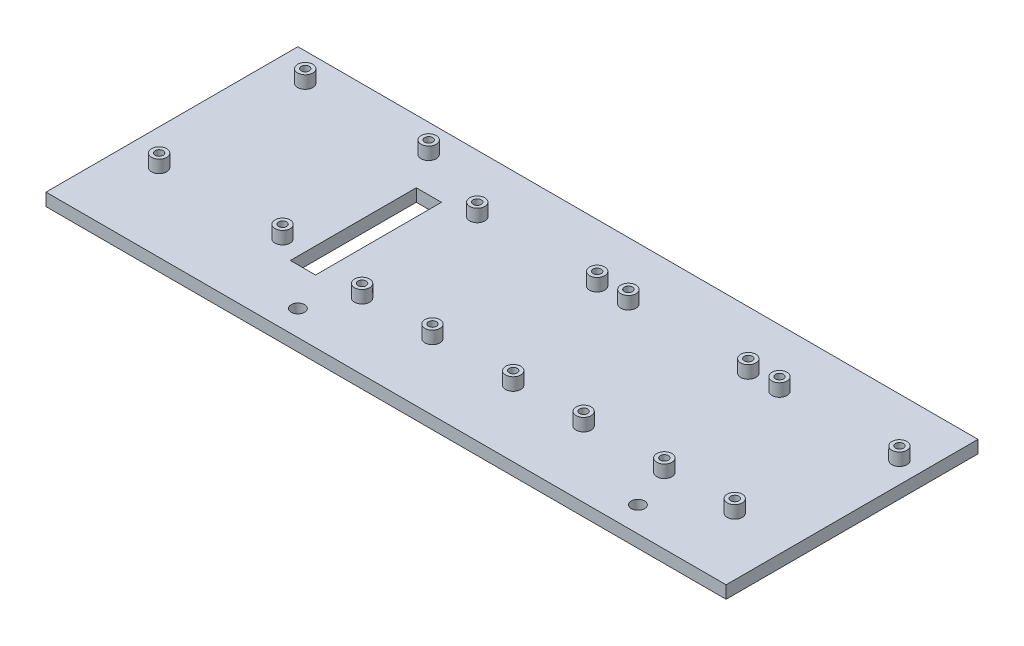
SolidWorks part; units mm, degrees
ref_plane "Front Plane" through (0, 0, 0) normal (0, 0, 1) x (1, 0, 0)
ref_plane "Top Plane" through (0, 0, 0) normal (0, 1, 0) x (1, 0, 0)
ref_plane "Right Plane" through (0, 0, 0) normal (1, 0, 0) x (0, 0, -1)
sketch "Sketch1" plane through (0, 0, 0) normal (0, 1, 0) x (1, 0, 0)
  line L1 (0, 0) -> (270, 0)
  line L2 (0, 0) -> (0, 100)
  line L3 (0, 100) -> (270, 100)
  line L4 (270, 0) -> (270, 100)
  dimension "D1" = 270
  dimension "D2" = 100
extrude "Boss-Extrude1" add sketch "Sketch1" along normal blind 5
sketch "Sketch2" plane through (0, 5, 0) normal (0, 1, 0) x (1, 0, 0)
  line L0 (150.83, 92.803) -> (204.83, 92.803)
  line L1 (10.5038, 92.4135) -> (66.5038, 92.4135)
  line L2 (10.5038, 92.4135) -> (10.5038, 7.4135)
  line L3 (10.5038, 7.4135) -> (66.5038, 7.4135)
  line L4 (66.5038, 92.4135) -> (66.5038, 7.4135)
  line L5 (90.8313, 92.4135) -> (144.8313, 92.4135)
  line L6 (90.8313, 92.4135) -> (90.8313, 23.9135)
  line L7 (90.8313, 23.9135) -> (144.8313, 23.9135)
  line L8 (144.8313, 92.4135) -> (144.8313, 23.9135)
  line L9 (150.83, 92.803) -> (150.83, 24.303)
  line L10 (150.83, 24.303) -> (204.83, 24.303)
  line L11 (204.83, 92.803) -> (204.83, 24.303)
  line L12 (210.8288, 93.1925) -> (264.8288, 93.1925)
  line L13 (210.8288, 93.1925) -> (210.8288, 24.6925)
  line L14 (210.8288, 24.6925) -> (264.8288, 24.6925)
  line L15 (264.8288, 93.1925) -> (264.8288, 24.6925)
  dimension "D1" = 85
  dimension "D2" = 56
  dimension "D3" = 54
  dimension "D4" = 68.5
  dimension "D5" = 3
sketch "Sketch3" plane through (0, 5, 0) normal (0, 1, 0) x (1, 0, 0)
  line L0 (14.0038, 88.9135) -> (63.0038, 88.9135)
  line L1 (14.0038, 88.9135) -> (14.0038, 30.9135)
  line L2 (10.5038, 92.4135) -> (66.5038, 92.4135) construction
  line L3 (10.5038, 92.4135) -> (10.5038, 7.4135) construction
  circle A0 centre (14.0038, 88.9135) radius 1.6
  circle A1 centre (63.0038, 88.9135) radius 1.6
  circle A2 centre (63.0038, 30.9135) radius 1.6
  circle A3 centre (14.0038, 30.9135) radius 1.6
  circle A4 centre (14.0038, 88.9135) radius 3
  circle A5 centre (63.0038, 88.9135) radius 3
  circle A6 centre (63.0038, 30.9135) radius 3
  circle A7 centre (14.0038, 30.9135) radius 3
  point P12 (19.0668, 25.7223)
  dimension "D1" = 3.2
  dimension "D2" = 6
  dimension "D3" = 49
  dimension "D4" = 49
  dimension "D5" = 58
  dimension "D6" = 58
  dimension "D7" = 3.5
  dimension "D8" = 3.5
extrude "Boss-Extrude2" add sketch "Sketch3" along normal blind 5 contours A7 A3 | A5 A1 | A6 A2 | L0 A0 L1 | L1 A0 L0 | A4 region at (13.7774, 5, -89.1399) region at (14.6828, 5, -88.2345) region at (63.0038, 5, -91.8287) region at (16.0651, 5, -32.9748) region at (60.0886, 5, -30.9135)
sketch "Sketch4" plane through (0, 5, 0) normal (0, 1, 0) x (1, 0, 0)
  circle A0 centre (14.0038, 88.9135) radius 1.6
  circle A1 centre (63.0038, 88.9135) radius 1.6
  circle A2 centre (63.0038, 30.9135) radius 1.6
  circle A3 centre (14.0038, 30.9135) radius 1.6
  dimension "D1" = 3.2
  dimension "D2" = 3.2
  dimension "D3" = 3.2
  dimension "D4" = 3.2
extrude "Cut-Extrude1" cut sketch "Sketch4" against normal blind 5
sketch "Sketch5" plane through (0, 0, 0) normal (0, -1, 0) x (-1, 0, 0)
  circle A0 centre (-63.0038, 88.9135) radius 3.25
  circle A1 centre (-14.0038, 88.9135) radius 3.25
  circle A2 centre (-14.0038, 30.9135) radius 3.25
  circle A3 centre (-63.0038, 30.9135) radius 3.25
  dimension "D1" = 6.5
  dimension "D2" = 2
  dimension "D3" = 2
extrude "Cut-Extrude2" cut sketch "Sketch5" against normal blind 3.2
sketch "Sketch6" plane through (0, 5, 0) normal (0, 1, 0) x (1, 0, 0)
  line L0 (94.0313, 77.1735) -> (141.6313, 77.1735)
  line L1 (90.8313, 92.4135) -> (144.8313, 92.4135) construction
  line L2 (144.8313, 92.4135) -> (144.8313, 23.9135) construction
  line L3 (90.8313, 92.4135) -> (90.8313, 23.9135) construction
  circle A0 centre (99.1113, 26.3735) radius 1.6
  circle A1 centre (127.0513, 26.3735) radius 1.6
  circle A2 centre (94.0313, 77.1735) radius 1.6
  circle A3 centre (141.6313, 77.1735) radius 1.6
  circle A4 centre (154.0313, 77.1735) radius 1.6
  circle A5 centre (159.1113, 26.3735) radius 1.6
  circle A6 centre (187.0513, 26.3735) radius 1.6
  circle A7 centre (201.6313, 77.1735) radius 1.6
  circle A8 centre (214.0313, 77.1735) radius 1.6
  circle A9 centre (219.1113, 26.3735) radius 1.6
  circle A10 centre (247.0513, 26.3735) radius 1.6
  circle A11 centre (261.6313, 77.1735) radius 1.6
  point P14 (0, 0)
  point P15 (0, 0)
  point P32 (0, 0)
  dimension "D1" = 3.2
  dimension "D2" = 15.24
  dimension "D3" = 50.8
  dimension "D4" = 50.8
  dimension "D5" = 17.78
  dimension "D6" = 66.04
  dimension "D7" = 45.72
  dimension "D8" = 66.04
  dimension "D9" = 3
extrude "Cut-Extrude3" cut sketch "Sketch6" against normal blind 23.2 contours A4 | A3 | A2 | A0 | A1 | A5 | A6 | A7 | A8 | A11 | A10 | A9 region at (141.6313, 5, -78.7283) region at (92.4766, 5, -77.1735) region at (99.1113, 5, -26.3735) region at (127.0513, 5, -26.3735) region at (154.0313, 5, -77.1735) region at (159.1113, 5, -26.3735)
sketch "Sketch7" plane through (0, 5, 0) normal (0, 1, 0) x (1, 0, 0)
  circle A0 centre (94.0313, 77.1735) radius 3
  circle A1 centre (141.6313, 77.1735) radius 3
  circle A2 centre (127.0513, 26.3735) radius 3
  circle A3 centre (99.1113, 26.3735) radius 3
  circle A4 centre (94.0313, 77.1735) radius 1.6
  circle A5 centre (141.6313, 77.1735) radius 1.6
  circle A6 centre (127.0513, 26.3735) radius 1.6
  circle A7 centre (99.1113, 26.3735) radius 1.6
  dimension "D1" = 6
extrude "Boss-Extrude3" add sketch "Sketch7" along normal blind 5
sketch "Sketch8" plane through (0, 0, 0) normal (0, -1, 0) x (1, 0, 0)
  circle A0 centre (94.0313, -77.1735) radius 3.25
  circle A1 centre (99.1113, -26.3735) radius 3.25
  circle A2 centre (127.0513, -26.3735) radius 3.25
  circle A3 centre (141.6313, -77.1735) radius 3.25
  dimension "D1" = 6.5
extrude "Cut-Extrude4" cut sketch "Sketch8" against normal blind 3.2
pattern_linear "LPattern1" count 3 spacing 60 along (1, 0, 0) of "Cut-Extrude4", "Boss-Extrude3"
sketch "Sketch9" plane through (0, 5, 0) normal (0, 1, 0) x (1, 0, 0)
  line L0 (0, 0) -> (270, 0) construction
  line L1 (72, 75) -> (82, 75)
  line L2 (72, 75) -> (72, 25)
  line L3 (72, 25) -> (82, 25)
  line L4 (82, 75) -> (82, 25)
  line L5 (0, 100) -> (0, 0) construction
  dimension "D1" = 10
  dimension "D2" = 50
  dimension "D3" = 25
  dimension "D4" = 72
extrude "Cut-Extrude5" cut sketch "Sketch9" against normal blind 13.2
sketch "Sketch10" plane through (0, 5, 0) normal (0, 1, 0) x (1, 0, 0)
  line L0 (0, 0) -> (270, 0) construction
  line L1 (270, 0) -> (270, 100) construction
  circle A0 centre (225, 10) radius 2.65
  circle A1 centre (90, 10) radius 2.65
  dimension "D1" = 5.3
  dimension "D2" = 5.3
  dimension "D3" = 135
  dimension "D4" = 10
  dimension "D5" = 10
  dimension "D6" = 45
extrude "Cut-Extrude6" cut sketch "Sketch10" against normal blind 23.2
